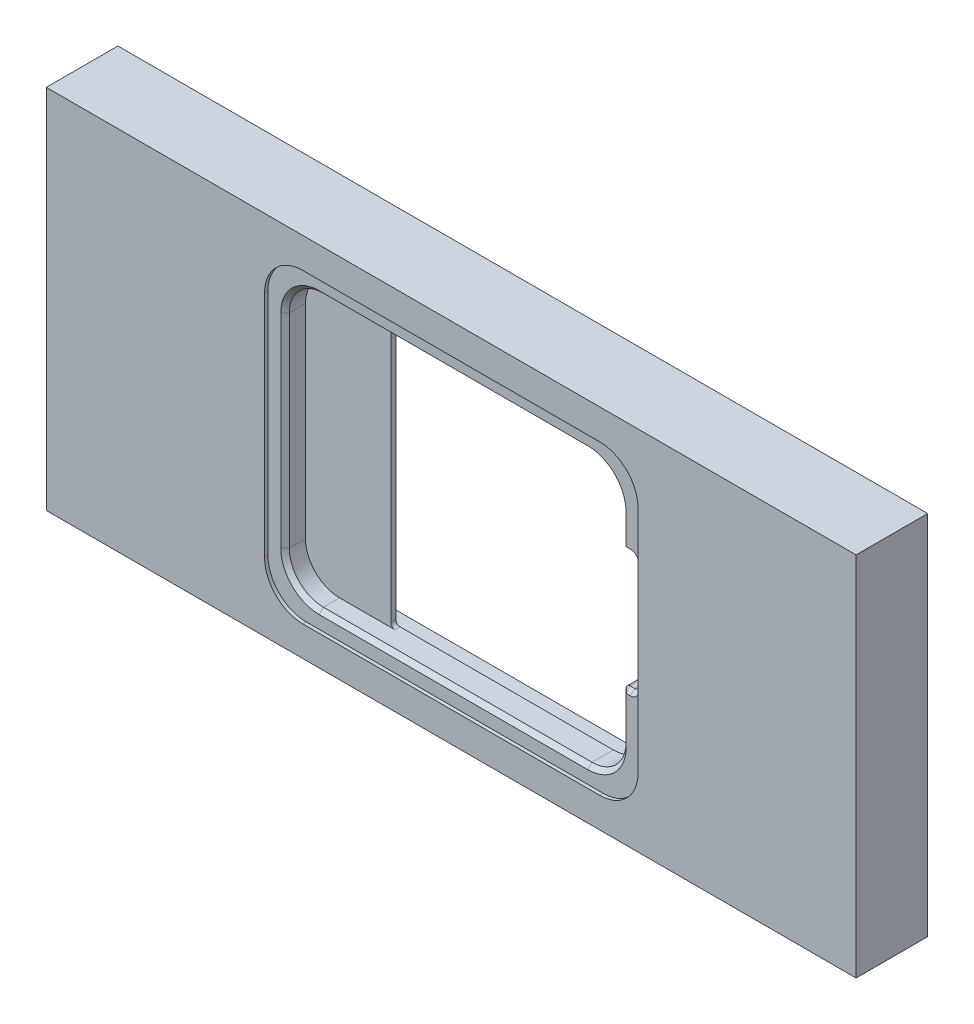
SolidWorks part; units mm, degrees
ref_plane "前视基准面" through (0, 0, 0) normal (0, 0, 1) x (1, 0, 0)
ref_plane "上视基准面" through (0, 0, 0) normal (0, 1, 0) x (1, 0, 0)
ref_plane "右视基准面" through (0, 0, 0) normal (1, 0, 0) x (0, 0, -1)
other "Configuration Table"
sketch "草图2" plane through (0, 0, 0) normal (0, 0, 1) x (1, 0, 0)
  line L0 (81.4875, 0.4873) -> (8.5127, 0.4873) construction
  line L1 (-2.4873, 2.4873) -> (92.4875, 2.4873)
  line L2 (-2.4873, 2.4873) -> (-2.4873, -40.4874)
  line L3 (-2.4873, -40.4874) -> (92.4875, -40.4874)
  line L4 (92.4875, 2.4873) -> (92.4875, -40.4874)
  line L5 (-0.4873, 0.4873) -> (90.4875, 0.4873)
  line L6 (-0.4873, 0.4873) -> (-0.4873, -38.4874)
  line L7 (-0.4873, -38.4874) -> (90.4875, -38.4874)
  line L8 (90.4875, 0.4873) -> (90.4875, -38.4874)
  line L9 (-0.4873, -8.5127) -> (-0.4873, -29.4874) construction
  line L10 (8.5127, -38.4874) -> (81.4875, -38.4874) construction
  line L11 (90.4875, -29.4874) -> (90.4875, -8.5127) construction
extrude "凸台-拉伸1" add sketch "草图2" along normal blind 5
sketch "草图3" plane through (0, 0, 5) normal (0, 0, 1) x (1, 0, 0)
  line L1 (-2.4873, 2.4873) -> (92.4875, 2.4873)
  line L2 (-2.4873, 2.4873) -> (-2.4873, -40.4874)
  line L3 (-2.4873, -40.4874) -> (92.4875, -40.4874)
  line L4 (92.4875, 2.4873) -> (92.4875, -40.4874)
extrude "凸台-拉伸2" add sketch "草图3" along normal blind 3.4
sketch "草图4" plane through (0, 0, 8.4) normal (0, 0, 1) x (1, 0, 0)
  line L0 (0.0127, -9) -> (0.0127, -2) construction
  line L1 (23.1127, -1.0627) -> (66.9127, -1.0627)
  line L2 (23.1127, -1.0627) -> (23.1127, -36.9627)
  line L3 (23.1127, -36.9627) -> (66.9127, -36.9627)
  line L4 (66.9127, -1.0627) -> (66.9127, -36.9627)
  line L5 (2, -0.0127) -> (88.0002, -0.0127) construction
  dimension "D1" = 35.9
  dimension "D2" = 43.8
  dimension "D3" = 23.1
  dimension "D4" = 1.05
extrude "切除-拉伸1" cut sketch "草图4" against normal blind 0.4
fillet "圆角1" radius 4.5 4 edges at (66.9127, -36.9627, 8.2) (23.1127, -36.9627, 8.2) (66.9127, -1.0627, 8.2) (23.1127, -1.0627, 8.2)
sketch "草图5" plane through (0, 0, 8) normal (0, 0, 1) x (1, 0, 0)
  line L0 (62.4127, -1.0627) -> (27.6127, -1.0627) construction
  line L1 (25.1127, -3.0627) -> (64.6127, -3.0627)
  line L2 (25.1127, -3.0627) -> (25.1127, -34.9627)
  line L3 (25.1127, -34.9627) -> (64.6127, -34.9627)
  line L4 (64.6127, -3.0627) -> (64.6127, -11.0627)
  line L5 (27.6127, -36.9627) -> (62.4127, -36.9627) construction
  line L6 (23.1127, -5.5627) -> (23.1127, -32.4627) construction
  line L7 (66.9127, -32.4627) -> (66.9127, -5.5627) construction
  line L8 (64.6127, -11.0627) -> (66.1127, -11.0627)
  line L9 (66.1127, -11.0627) -> (66.1127, -24.9627)
  line L10 (66.1127, -24.9627) -> (64.6127, -24.9627)
  line L11 (64.6127, -24.9627) -> (64.6127, -34.9627)
  dimension "D1" = 2
  dimension "D2" = 2
  dimension "D3" = 2
  dimension "D4" = 2.3
  dimension "D5" = 10
  dimension "D6" = 8
  dimension "D7" = 1.5
extrude "切除-拉伸2" cut sketch "草图5" against normal blind 2.4
sketch "草图6" plane through (0, 0, 5.6) normal (0, 0, 1) x (1, 0, 0)
  line L7 (64.6127, -3.0627) -> (25.1127, -3.0627) construction
  line L8 (35.1127, -3.0627) -> (64.6127, -3.0627)
  line L9 (35.1127, -3.0627) -> (35.1127, -34.9627)
  line L10 (35.1127, -34.9627) -> (64.6127, -34.9627)
  line L11 (64.6127, -3.0627) -> (64.6127, -11.0627)
  line L12 (25.1127, -3.0627) -> (25.1127, -34.9627) construction
  line L13 (64.6127, -11.0627) -> (64.6127, -3.0627) construction
  line L14 (64.6127, -11.0627) -> (66.1127, -11.0627)
  line L15 (66.1127, -11.0627) -> (66.1127, -24.9627)
  line L16 (66.1127, -24.9627) -> (64.6127, -24.9627)
  line L17 (64.6127, -24.9627) -> (64.6127, -34.9627)
  dimension "D1" = 10
extrude "切除-拉伸3" cut sketch "草图6" against normal blind 0.6
fillet "圆角2" radius 4 4 edges at (25.1127, -3.0627, 6.8) (25.1127, -34.9627, 6.8) (64.6127, -3.0627, 6.5) (64.6127, -34.9627, 6.5)
fillet "圆角3" radius 0.5 6 edges at (35.1127, -3.0627, 5.3) (66.1127, -24.9627, 6.5) (66.1127, -11.0627, 6.5) (64.6127, -11.0627, 6.5) (64.6127, -24.9627, 6.5) (35.1127, -34.9627, 5.3)
chamfer "倒角1" distance 0.5 angle 45 16 edges at (65.9663, -24.8163, 8) (65.3627, -24.9627, 8) (66.1127, -18.0127, 8) (64.7591, -25.1091, 8) (65.9663, -11.2091, 8) (64.6127, -28.2127, 8) (65.3627, -11.0627, 8) (63.4411, -33.7911, 8) (64.7591, -10.9163, 8) (44.8627, -34.9627, 8) (64.6127, -8.8127, 8) (26.2843, -33.7911, 8) (63.4411, -4.2343, 8) (25.1127, -19.0127, 8) (44.8627, -3.0627, 8) (26.2843, -4.2343, 8)
